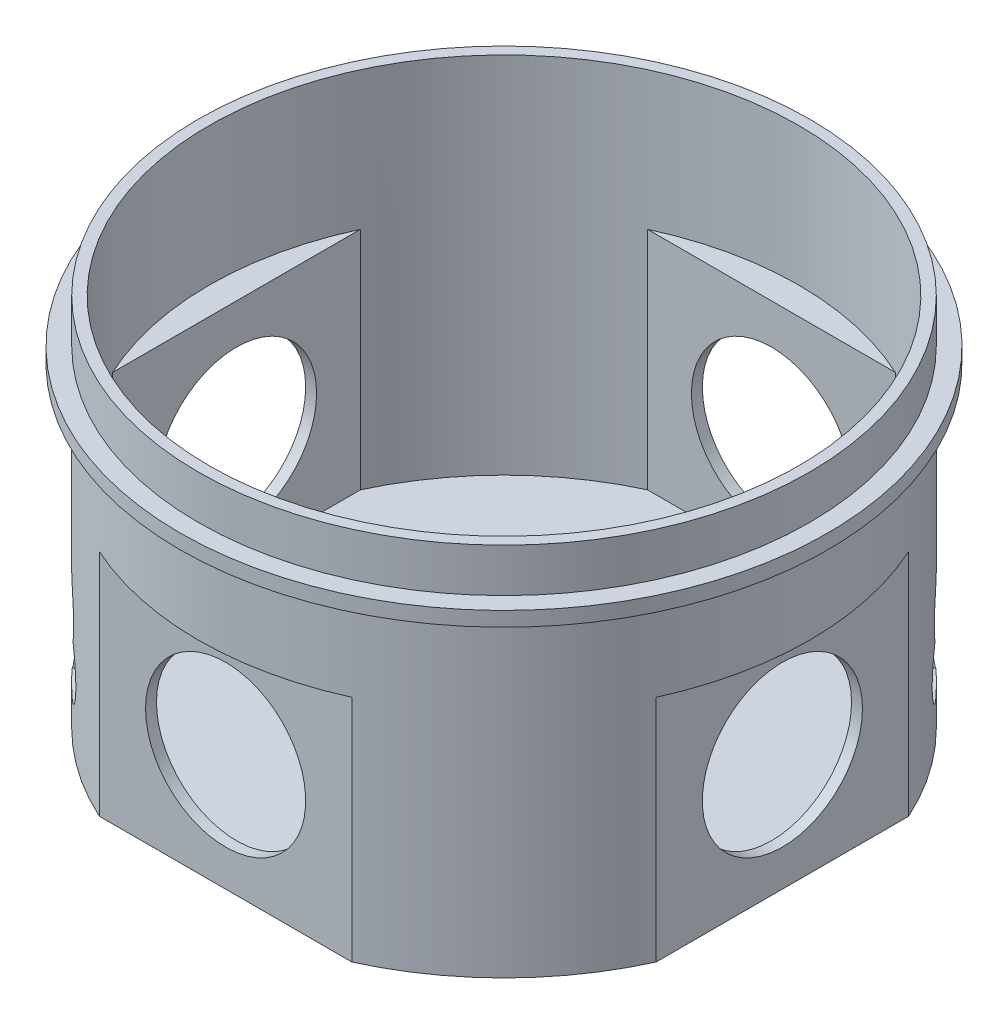
SolidWorks part; units mm, degrees
ref_plane "Спереди" through (0, 0, 0) normal (0, 0, 1) x (1, 0, 0)
ref_plane "Сверху" through (0, 0, 0) normal (0, 1, 0) x (1, 0, 0)
ref_plane "Справа" through (0, 0, 0) normal (1, 0, 0) x (0, 0, -1)
sketch "Эскиз1" plane through (0, 0, 0) normal (0, 1, 0) x (1, 0, 0)
  line L0 (0, 0) -> (0, 38.25) construction
  line L1 (-38.25, 38.25) -> (38.25, 38.25)
  line L2 (-38.25, 38.25) -> (-38.25, -38.25)
  line L3 (-38.25, -38.25) -> (38.25, -38.25)
  line L4 (38.25, 38.25) -> (38.25, -38.25)
  line L5 (0, 0) -> (38.25, 0) construction
  circle A0 centre (0, 0) radius 42
  dimension "D1" = 84
  dimension "D2" = 76.5
extrude "Бобышка-Вытянуть1" add sketch "Эскиз1" along normal blind 1.5 contours L3 A0 L4 L1 L2 region at (0, 0, 0)
sketch "Эскиз2" plane through (0, 1.5, 0) normal (0, 1, 0) x (1, 0, 0)
  line L4 (-17.0202, -36.75) -> (17.0202, -36.75)
  line L5 (36.75, -17.0202) -> (36.75, 17.0202)
  line L6 (17.0202, 36.75) -> (-17.0202, 36.75)
  line L7 (-36.75, 17.0202) -> (-36.75, -17.0202)
  line L8 (-17.3476, -38.25) -> (17.3476, -38.25)
  line L9 (38.25, -17.3476) -> (38.25, 17.3476)
  line L10 (17.3476, 38.25) -> (-17.3476, 38.25)
  line L11 (-38.25, 17.3476) -> (-38.25, -17.3476)
  line L12 (-17.3476, -38.25) -> (17.3476, -38.25)
  line L13 (38.25, -17.3476) -> (38.25, 17.3476)
  line L14 (17.3476, 38.25) -> (-17.3476, 38.25)
  line L15 (-38.25, 17.3476) -> (-38.25, -17.3476)
  arc A4 (17.0202, -36.75) -> (36.75, -17.0202) centre (0, 0) ccw
  arc A5 (36.75, 17.0202) -> (17.0202, 36.75) centre (0, 0) ccw
  arc A6 (-17.0202, 36.75) -> (-36.75, 17.0202) centre (0, 0) ccw
  arc A7 (-36.75, -17.0202) -> (-17.0202, -36.75) centre (0, 0) ccw
  arc A8 (17.3476, -38.25) -> (38.25, -17.3476) centre (0, 0) ccw
  arc A9 (38.25, 17.3476) -> (17.3476, 38.25) centre (0, 0) ccw
  arc A10 (-17.3476, 38.25) -> (-38.25, 17.3476) centre (0, 0) ccw
  arc A11 (-38.25, -17.3476) -> (-17.3476, -38.25) centre (0, 0) ccw
  arc A12 (17.3476, -38.25) -> (38.25, -17.3476) centre (0, 0) ccw
  arc A13 (38.25, 17.3476) -> (17.3476, 38.25) centre (0, 0) ccw
  arc A14 (-17.3476, 38.25) -> (-38.25, 17.3476) centre (0, 0) ccw
  arc A15 (-38.25, -17.3476) -> (-17.3476, -38.25) centre (0, 0) ccw
  dimension "D1" = 0
  dimension "D2" = 1.5
extrude "Бобышка-Вытянуть2" add sketch "Эскиз2" along normal blind 30
sketch "Эскиз3" plane through (0, 31.5, 0) normal (0, 1, 0) x (1, 0, 0)
  circle A0 centre (0, 0) radius 42
  circle A1 centre (0, 0) radius 40.5
  arc M1 (-38.25, -17.3476) -> (-17.3476, -38.25) centre (0, 0) ccw
  line M2 (-17.3476, -38.25) -> (17.3476, -38.25)
  arc M3 (17.3476, -38.25) -> (38.25, -17.3476) centre (0, 0) ccw
  line M4 (38.25, -17.3476) -> (38.25, 17.3476)
  arc M5 (38.25, 17.3476) -> (17.3476, 38.25) centre (0, 0) ccw
  line M6 (17.3476, 38.25) -> (-17.3476, 38.25)
  arc M7 (-17.3476, 38.25) -> (-38.25, 17.3476) centre (0, 0) ccw
  line M8 (-38.25, 17.3476) -> (-38.25, -17.3476)
  line M9 (17.0202, -36.75) -> (-17.0202, -36.75)
  arc M10 (-17.0202, -36.75) -> (-36.75, -17.0202) centre (0, 0) cw
  line M11 (-36.75, -17.0202) -> (-36.75, 17.0202)
  arc M12 (-36.75, 17.0202) -> (-17.0202, 36.75) centre (0, 0) cw
  line M13 (-17.0202, 36.75) -> (17.0202, 36.75)
  arc M14 (17.0202, 36.75) -> (36.75, 17.0202) centre (0, 0) cw
  line M15 (36.75, 17.0202) -> (36.75, -17.0202)
  arc M16 (36.75, -17.0202) -> (17.0202, -36.75) centre (0, 0) cw
extrude "Бобышка-Вытянуть3" add sketch "Эскиз3" along normal blind 1 contours A1 M8 | A1 M11 M8 | A1 A0 M4 | A1 M4 | A1 M15 M4 | A1 M13 M6 | A1 M6 | A1 A0 M6 | A1 A0 M2 | A1 M2 | A1 M2 M9 | A1 M8 M1 M2 M10 | A1 M2 M3 M4 M16 | A1 M4 M5 M6 M14 | A1 M6 M7 M8 M12 | A1 A0 M8 region at (40.7107, 31.5, 8.8004) region at (37.8973, 31.5, -15.3294) region at (29.4491, 31.5, 29.4491) region at (15.3294, 31.5, -38.599) region at (37.4697, 31.5, 0) region at (39.1522, 31.5, 0) region at (0, 31.5, 41.651) region at (-15.3294, 31.5, -37.8973) region at (0, 31.5, -39.1522) region at (0, 31.5, -37.4697) region at (-29.4491, 31.5, 29.4491) region at (0, 31.5, 37.4697) region at (0, 31.5, 39.1522) region at (-38.599, 31.5, -15.3294) region at (-39.1522, 31.5, 0) region at (-37.4697, 31.5, 0)
sketch "Эскиз4" plane through (0, 32.5, 0) normal (0, 1, 0) x (1, 0, 0)
  circle A0 centre (0, 0) radius 42
  circle A1 centre (0, 0) radius 40.5
  circle A2 centre (0, 0) radius 42 construction
extrude "Бобышка-Вытянуть4" add sketch "Эскиз4" along normal blind 11
sketch "Эскиз5" plane through (0, 43.5, 0) normal (0, 1, 0) x (1, 0, 0)
  circle A0 centre (0, 0) radius 40.5 construction
  circle A1 centre (0, 0) radius 40.5
  circle A2 centre (0, 0) radius 44.5
  dimension "D1" = 89
extrude "Бобышка-Вытянуть5" add sketch "Эскиз5" along normal blind 2
sketch "Эскиз6" plane through (0, 45.5, 0) normal (0, 1, 0) x (1, 0, 0)
  circle A0 centre (0, 0) radius 42
  circle A1 centre (0, 0) radius 40.5 construction
  circle A2 centre (0, 0) radius 40.5
  dimension "D1" = 1.5
extrude "Бобышка-Вытянуть6" add sketch "Эскиз6" along normal blind 6
sketch "Эскиз7" plane through (38.25, 0, 0) normal (1, 0, 0) x (0, 0, -1)
  circle A0 centre (0, 16) radius 11
  point P2 (0, 5)
  dimension "D1" = 22
  dimension "D2" = 5
extrude "Вырез-Вытянуть1" cut sketch "Эскиз7" against normal through all
pattern_circular "Круговой массив1" count 2 every 90 about axis through (0, 51.5, 0) along (0, 1, 0) of "Вырез-Вытянуть1"
ref_plane "Плоскость1" through (0, 0, 0) normal (-0.7071, 0, 0.7071) x (0.7071, 0, 0.7071)
sketch "Эскиз8" plane through (0, 0, 0) normal (-0.7071, 0, 0.7071) x (0.7071, 0, 0.7071)
  line L0 (0, 0) -> (0, 15) construction
  line L1 (-4.2197, 9) -> (14.7803, 9) construction
  line L2 (14.7803, 31.5) -> (14.7803, 0) construction
  line L3 (-14.7803, 0) -> (14.7803, 0) construction
  circle A0 centre (-4.2197, 9) radius 4
  circle A1 centre (0, 15) radius 4
  circle A2 centre (1.7803, 9) radius 4
  point P6 (6.9995, 9)
  point P10 (2.1747, 9)
  dimension "D1" = 8
  dimension "D2" = 15
  dimension "D3" = 19
  dimension "D4" = 9
  dimension "D5" = 6
extrude "Вырез-Вытянуть2" cut sketch "Эскиз8" against normal through all both and the other way through all contours A1 | A0 | A2
